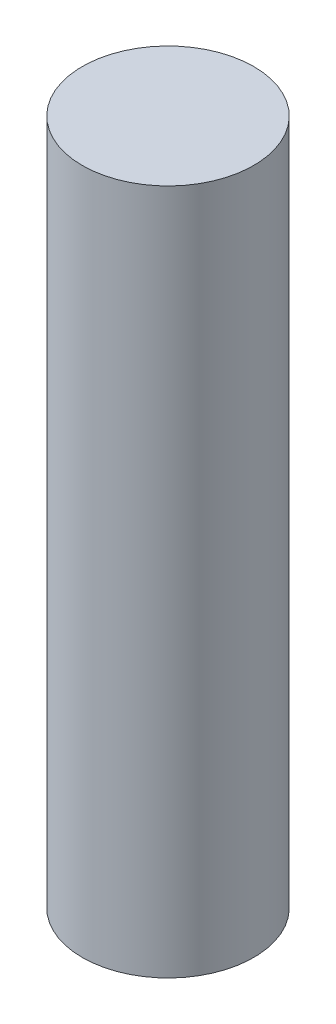
SolidWorks part; units mm, degrees
material "Brass"
ref_plane "Front Plane" through (0, 0, 0) normal (0, 0, 1) x (1, 0, 0)
ref_plane "Top Plane" through (0, 0, 0) normal (0, 1, 0) x (1, 0, 0)
ref_plane "Right Plane" through (0, 0, 0) normal (1, 0, 0) x (0, 0, -1)
sketch "Sketch1" plane through (0, 0, 0) normal (0, 1, 0) x (1, 0, 0)
  circle A0 centre (0, 0) radius 2.5
  dimension "D1" = 5
extrude "Boss-Extrude1" add sketch "Sketch1" along normal blind 20
ref_axis "Axis1" through (0, 20, 0) along (0, -1, 0)
